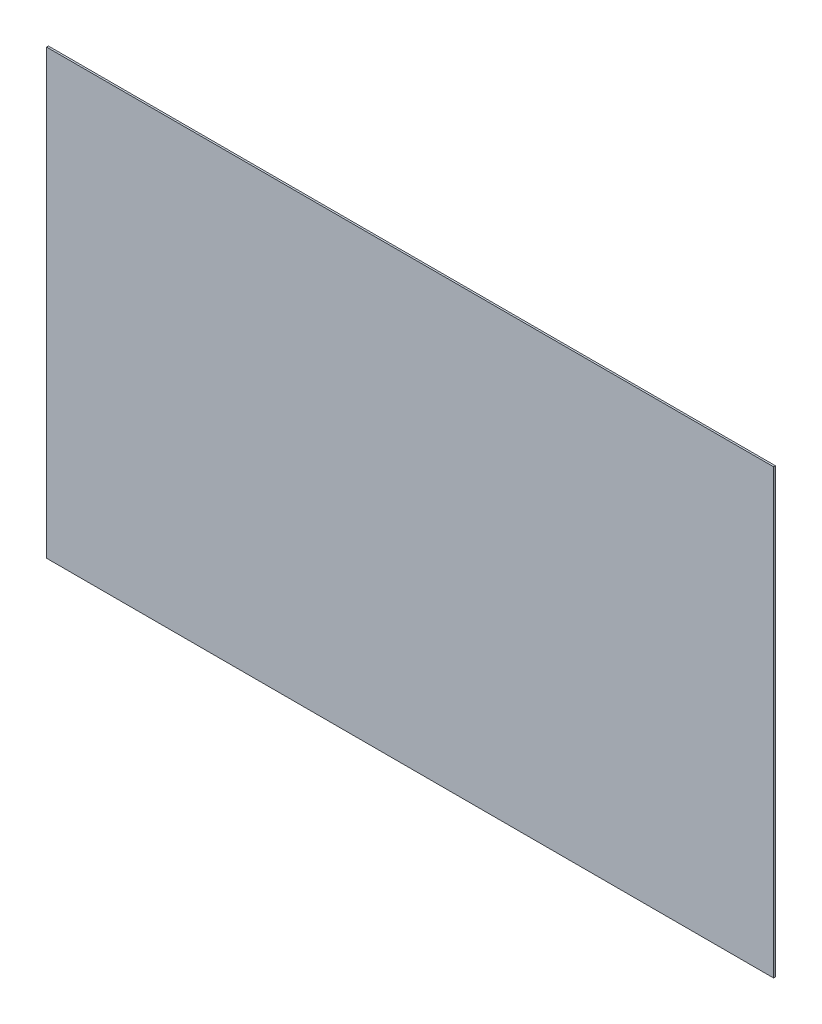
SolidWorks part; units mm, degrees
ref_plane "Front Plane" through (0, 0, 0) normal (0, 0, 1) x (1, 0, 0)
ref_plane "Top Plane" through (0, 0, 0) normal (0, 1, 0) x (1, 0, 0)
ref_plane "Right Plane" through (0, 0, 0) normal (1, 0, 0) x (0, 0, -1)
sketch "Sketch1" plane through (0, 0, 0) normal (0, 0, 1) x (1, 0, 0)
  line L1 (0, 0) -> (625.602, 0)
  line L2 (0, 0) -> (0, 381)
  line L3 (0, 381) -> (625.602, 381)
  line L4 (625.602, 0) -> (625.602, 381)
  dimension "D1" = 381
  dimension "D2" = 625.602
extrude "Boss-Extrude1" add sketch "Sketch1" along normal blind 1.5875
